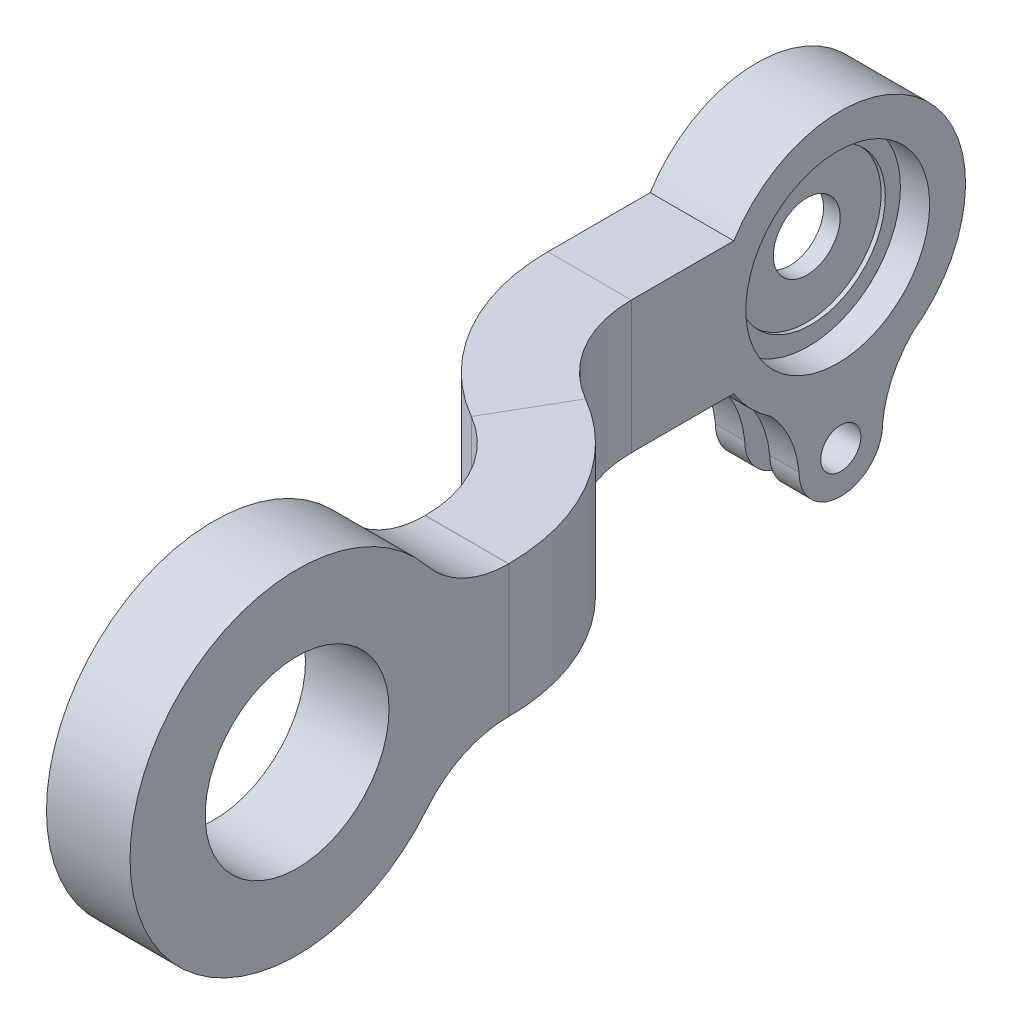
SolidWorks part; units mm, degrees
material "Resina de melamina"
ref_plane "Alzado" through (0, 0, 0) normal (0, 0, 1) x (1, 0, 0)
ref_plane "Planta" through (0, 0, 0) normal (0, 1, 0) x (1, 0, 0)
ref_plane "Vista lateral" through (0, 0, 0) normal (1, 0, 0) x (0, 0, -1)
sketch "Croquis1" plane through (0, 0, 0) normal (0, 1, 0) x (1, 0, 0)
  line L0 (0, 0) -> (0, 60) construction
  line L1 (0, 60) -> (-20, 60) construction
  line L2 (-20, 60) -> (-20, 85) construction
  line L3 (0, 15) -> (-20, 25.359) construction
  line L4 (-20, 85) -> (-20, 60)
  line L5 (0, 25.359) -> (0, 0)
  arc A0 (-20, 60) -> (-10, 42.6795) centre (0, 60) ccw
  arc A1 (0, 25.359) -> (-10, 42.6795) centre (-20, 25.359) ccw
  dimension "D4" = 20
  dimension "D1" = 60
  dimension "D2" = 25
  dimension "D3" = 20
sketch "Croquis2" plane through (0, 0, 0) normal (0, 0, 1) x (1, 0, 0)
  line L1 (5, -7.9175) -> (-5, -7.9175)
  line L2 (5, -7.9175) -> (5, 7.9175)
  line L3 (5, 7.9175) -> (-5, 7.9175)
  line L4 (-5, -7.9175) -> (-5, 7.9175)
  line L5 (5, -7.9175) -> (-5, 7.9175) construction
  line L6 (5, 7.9175) -> (-5, -7.9175) construction
  point P0 (0, 0)
  dimension "D1" = 10
sweep "Barrer1" add profiles "Croquis2" path "Croquis1"
sketch "Croquis4" plane through (-15, 0, 0) normal (1, 0, 0) x (0, 0, -1)
  line L1 (85, -7.9175) -> (85, 7.9175) construction
  circle A0 centre (85, 0) radius 15
  dimension "D2" = 30
extrude "Saliente-Extruir1" add sketch "Croquis4" against normal blind 10
sketch "Croquis5" plane through (5, 0, 0) normal (1, 0, 0) x (0, 0, -1)
  circle A0 centre (0, 0) radius 20
  dimension "D1" = 40
extrude "Saliente-Extruir2" add sketch "Croquis5" against normal blind 10
sketch "Croquis6" plane through (-15, 0, 0) normal (1, 0, 0) x (0, 0, -1)
  line L0 (60, 0) -> (85, 0) construction
  circle A0 centre (85, 0) radius 4
  dimension "D1" = 8
sketch "Croquis7" plane through (5, 0, 0) normal (1, 0, 0) x (0, 0, -1)
  circle A0 centre (0, 0) radius 11
  dimension "D1" = 22
ref_plane "Plano1" through (-15, 0, 0) normal (1, 0, 0) x (0, 0, -1)
sketch "Croquis12" plane through (-15, 0, 0) normal (1, 0, 0) x (0, 0, -1)
  line L0 (85.0685, -0.0274) -> (85.0685, 24.9726) construction
  line L1 (85.0685, 24.9726) -> (85.0685, 19.9726) construction
  line L2 (85.0685, 24.9726) -> (85.0685, 14.9726) construction
  arc A0 (90.0685, 19.9726) -> (80.0685, 19.9726) centre (85.0685, 19.9726) ccw
  arc A1 (94.2885, 11.6439) -> (75.8485, 11.6439) centre (85.0685, -0.0274) ccw
  spline S0 degree 2 poles (80.0685, 19.9726) (79.5667, 15.0283) (75.8485, 11.6439) knots 0 0 0 1 1 1
  spline S1 degree 2 poles (90.0685, 19.9726) (90.5703, 15.0283) (94.2885, 11.6439) knots 0 0 0 1 1 1
  dimension "D1" = 25
  dimension "D2" = 5
extrude "Saliente-Extruir5" add sketch "Croquis12" against normal blind 3.5
ref_plane "Plano2" through (-20, 0, 0) normal (1, 0, 0) x (0, 0, -1)
mirror "Simetría1" about plane through (-20, 0, 0) normal (1, 0, 0) of "Saliente-Extruir5"
sketch "Croquis13" plane through (-15, 0, 0) normal (1, 0, 0) x (0, 0, -1)
  circle A0 centre (85.0685, 19.9726) radius 2.5
  dimension "D1" = 5
extrude "Cortar-Extruir1" cut sketch "Croquis13" against normal blind 10
mirror "Simetría3" about plane through (0, 0, 0) normal (0, 1, 0) of "Simetría1"
sketch "Croquis20" plane through (-15, 0, 0) normal (1, 0, 0) x (0, 0, -1)
  line L0 (60, 0) -> (85, 0) construction
  line L2 (75.9168, 25.7358) -> (95.1724, 25.7358)
  line L3 (75.9168, 25.7358) -> (75.9168, 11.9372)
  line L5 (95.1724, 25.7358) -> (95.1724, 11.0237)
  arc A0 (95.1724, 11.0237) -> (75.9168, 11.9372) centre (85, 0) ccw
extrude "Cortar-Extruir5" cut sketch "Croquis20" against normal blind 10
sketch "Croquis21" plane through (-25, 0, 0) normal (-1, 0, 0) x (0, 0, 1)
  circle A0 centre (-85.0685, -19.9726) radius 2.4
  dimension "D1" = 4.8
extrude "Cortar-Extruir6" cut sketch "Croquis21" against normal blind 10
extrude "Cortar-Extruir7" cut sketch "Croquis7" against normal blind 10
fillet "Redondeo1" radius 12.5 1 edges at (0, -7.9175, -18.3661) type face fillet first side face at (0, 0, 0.8169) second side face at (0, -7.9175, -21.8625)
fillet "Redondeo2" radius 12.5 1 edges at (0, 7.9175, -18.3661) type face fillet first side face at (0, 0.1953, 1.4258) second side face at (0, 7.9175, -21.8625)
sketch "Croquis22" plane through (-25, 0, 0) normal (-1, 0, 0) x (0, 0, 1)
  circle A0 centre (-85, 0) radius 11.5
  dimension "D1" = 23
extrude "Cortar-Extruir8" cut sketch "Croquis22" against normal blind 4
extrude "Cortar-Extruir9" cut sketch "Croquis6" against normal blind 8
sketch "Croquis23" plane through (-15, 0, 0) normal (1, 0, 0) x (0, 0, -1)
  circle A0 centre (84.7046, 0) radius 11
  dimension "D1" = 22
extrude "Cortar-Extruir10" cut sketch "Croquis23" against normal blind 4
sketch "Croquis24" plane through (-19, 0, 0) normal (1, 0, 0) x (0, 0, -1)
  circle A0 centre (85, 0) radius 11.2954
  circle A1 centre (85, 0) radius 8.9
  dimension "D1" = 17.8
extrude "Saliente-Extruir6" add sketch "Croquis24" along normal blind 0.5
sketch "Croquis25" plane through (-21, 0, 0) normal (-1, 0, 0) x (0, 0, 1)
  circle A0 centre (-85, 0) radius 11.5
  circle A1 centre (-85, 0) radius 8.9
  dimension "D1" = 17.8
extrude "Saliente-Extruir7" add sketch "Croquis25" along normal blind 0.5
equation "\"3.5.00mm\"=3"
